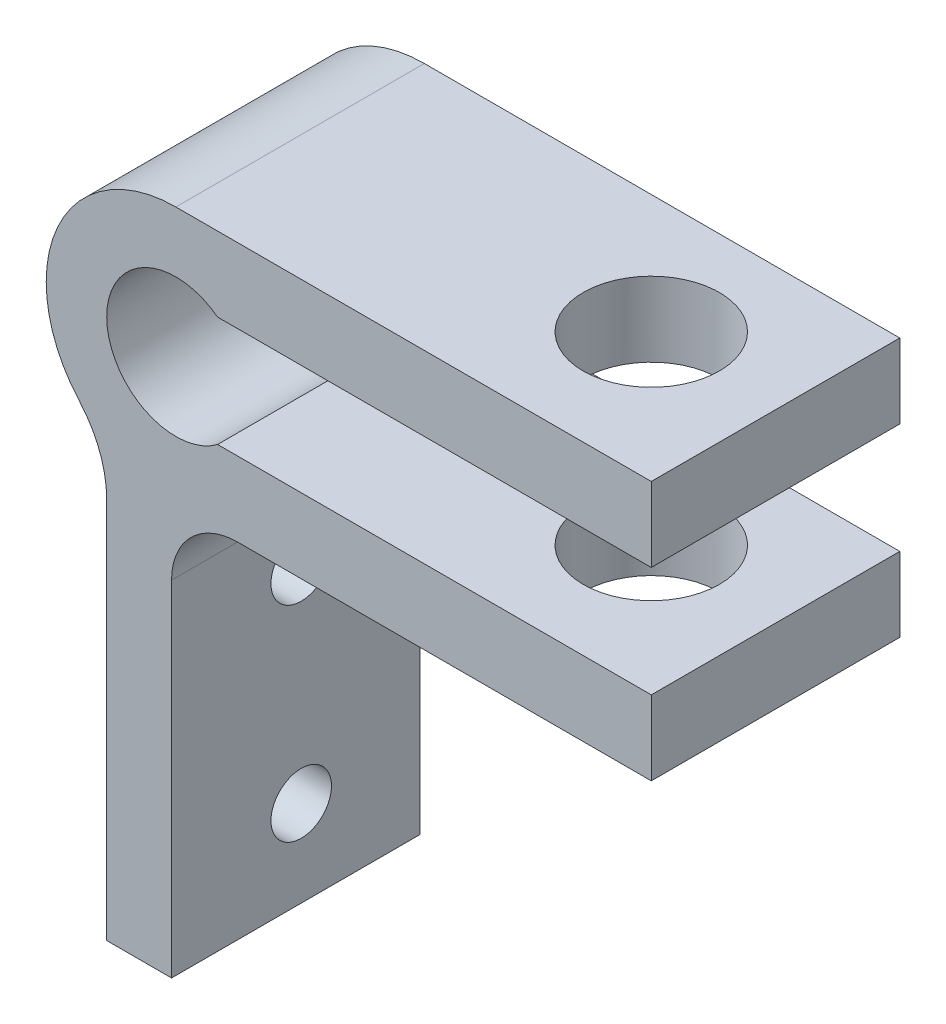
SolidWorks part; units mm, degrees
material "ABS"
ref_plane "Front Plane" through (0, 0, 0) normal (0, 0, 1) x (1, 0, 0)
ref_plane "Top Plane" through (0, 0, 0) normal (0, 1, 0) x (1, 0, 0)
ref_plane "Right Plane" through (0, 0, 0) normal (1, 0, 0) x (0, 0, -1)
sketch "Sketch1" plane through (0, 0, 0) normal (0, 0, 1) x (1, 0, 0)
  line L0 (10, 6) -> (22, 6)
  line L1 (22, 6) -> (22, 2.5527)
  line L2 (22, 2.5527) -> (1.9297, 2.5527)
  line L3 (-11.5353, 0) -> (18.1518, 0) construction
  line L4 (22, -2.5527) -> (1.9297, -2.5527)
  line L5 (22, -6) -> (22, -2.5527)
  line L6 (22, -6) -> (2.8549, -6)
  line L7 (10, 6) -> (5, 6)
  line L8 (-3.2, -6) -> (-3.2, -5.0754)
  line L10 (0, 6) -> (5, 6)
  line L11 (-0.2, -25) -> (-0.2, -9.0549)
  line L12 (-3.2, -25) -> (-0.2, -25)
  line L13 (-3.2, -6) -> (-3.2, -25)
  arc A0 (1.9297, 2.5527) -> (1.9297, -2.5527) centre (0, 0) ccw
  arc A2 (0, 6) -> (-3.2, -5.0754) centre (0, 0) ccw
  arc A3 (-0.2, -9.0549) -> (2.8549, -6) centre (2.8549, -9.0549) cw
  dimension "D1" = 3.2
  dimension "D2" = 6
  dimension "D5" = 3
  dimension "D3" = 22
  dimension "D4" = 5.1054
extrude "Boss-Extrude1" add sketch "Sketch1" along normal blind 12
sketch "Sketch2" plane through (0, 0, 0) normal (0, 1, 0) x (1, 0, 0)
  line L1 (16, -6) -> (5, -6) construction
  circle A0 centre (16, -6) radius 3.15
  dimension "D3" = 6.3
  dimension "D1" = 16
extrude "Cut-Extrude1" cut sketch "Sketch2" against normal through all and the other way through all
sketch "Sketch3" plane through (-0.2, 0, 0) normal (-1, 0, 0) x (0, 0, 1)
  line L3 (12, -25) -> (0, -25) construction
  circle A0 centre (6, -11.5) radius 1.4
  circle A1 centre (6, -21) radius 1.4
  line M12 (0, -9.0549) -> (12, -9.0549)
  dimension "D2" = 2.8
  dimension "D1" = 9.5
  dimension "D3" = 4
extrude "Cut-Extrude2" cut sketch "Sketch3" along normal through all both and the other way through all contours A0 | A1 | A0 M12 region at (-0.2, -11.5, 6) region at (-0.2, -21, 6)
chamfer "Chamfer1" distance 0.5 angle 45 12 edges at (11.9648, -2.5527, 0) (-3.2, 0, 0) (11.9648, 2.5527, 0) (22, -4.2764, 0) (0.6948, -6.8948, 0) (-0.2, -17.0274, 0) (-1.7, -25, 0) (-3.2, -15.0377, 0) (-5.7642, 1.6654, 0) (11, 6, 0) (22, 4.2764, 0) (12.4274, -6, 0)
fillet "Fillet1" radius 5 1 edges at (-3.2, -5.0754, 6.25)
